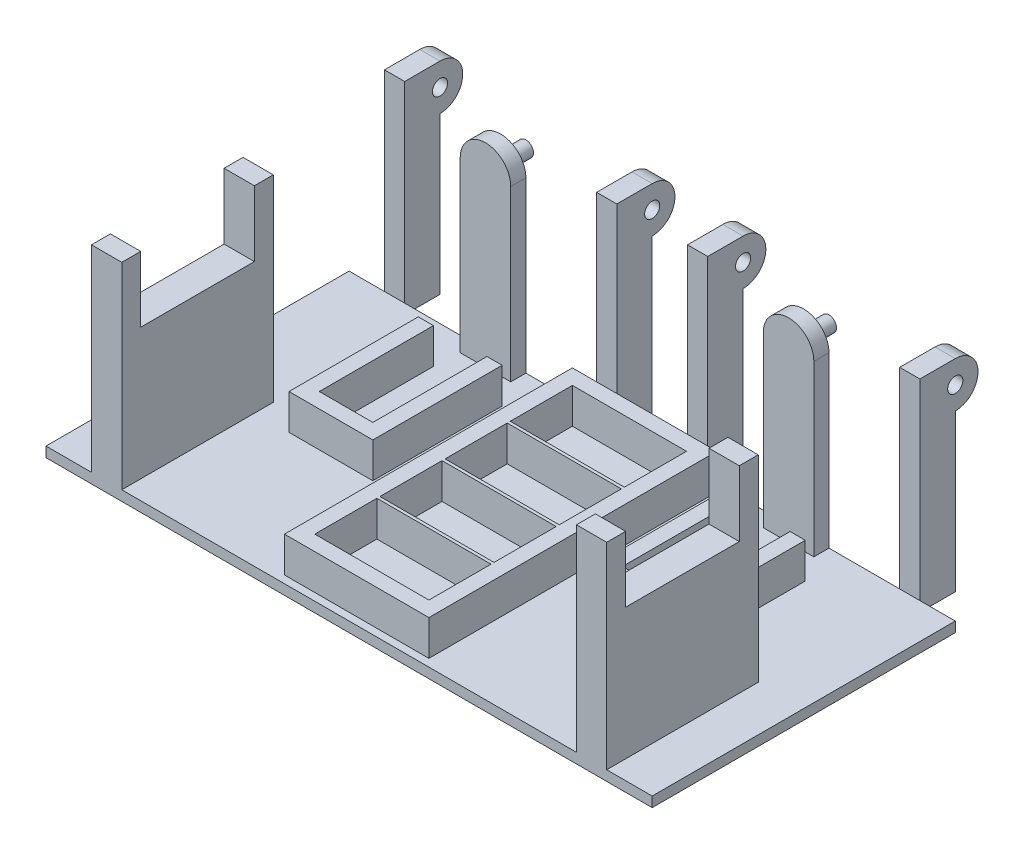
SolidWorks part; units mm, degrees
ref_plane "Front Plane" through (0, 0, 0) normal (0, 0, 1) x (1, 0, 0)
ref_plane "Top Plane" through (0, 0, 0) normal (0, 1, 0) x (1, 0, 0)
ref_plane "Right Plane" through (0, 0, 0) normal (1, 0, 0) x (0, 0, -1)
sketch "Sketch1" plane through (0, 0, 0) normal (0, 1, 0) x (1, 0, 0)
  line L0 (-60, -30) -> (-51, -30)
  line L1 (-60, -30) -> (60, -30)
  line L2 (-60, -30) -> (-60, 30)
  line L3 (-60, 30) -> (60, 30)
  line L4 (60, -30) -> (60, 30)
  line L5 (-60, -30) -> (60, 30) construction
  line L6 (-60, 30) -> (60, -30) construction
  line L7 (-51, -30) -> (-45, -30)
  line L8 (-45, -30) -> (-45, 0)
  line L9 (-45, 0) -> (-51, 0)
  line L10 (-51, 0) -> (-51, -30)
  line L11 (51, -30) -> (51, 0)
  line L12 (51, 0) -> (45, 0)
  line L13 (45, 0) -> (45, -30)
  line L14 (45, -30) -> (51, -30)
  line L15 (-38.3, 22) -> (-38.3, -3.6)
  line L16 (-38.3, -3.6) -> (-21.7, -3.6)
  line L17 (-21.7, -3.6) -> (-21.7, 22)
  line L18 (-21.7, 22) -> (-24.7, 22)
  line L19 (-24.7, 22) -> (-24.7, -0.6)
  line L20 (-24.7, -0.6) -> (-35.3, -0.6)
  line L21 (-35.3, -0.6) -> (-35.3, 22)
  line L22 (-35.3, 22) -> (-38.3, 22)
  line L23 (21.7, 22) -> (21.7, -3.6)
  line L24 (21.7, -3.6) -> (38.3, -3.6)
  line L25 (38.3, -3.6) -> (38.3, 22)
  line L26 (38.3, 22) -> (35.3, 22)
  line L27 (35.3, 22) -> (35.3, -0.6)
  line L28 (35.3, -0.6) -> (24.7, -0.6)
  line L29 (24.7, -0.6) -> (24.7, 22)
  line L30 (24.7, 22) -> (21.7, 22)
  line L31 (-25, 30) -> (-25, 27)
  line L32 (-25, 27) -> (-35, 27)
  line L33 (-35, 27) -> (-35, 30)
  line L34 (-35, 30) -> (-25, 30)
  line L35 (25, 30) -> (25, 27)
  line L36 (25, 27) -> (35, 27)
  line L37 (35, 27) -> (35, 30)
  line L38 (35, 30) -> (25, 30)
  line L39 (-53, 30) -> (-53, 37)
  line L40 (-53, 37) -> (-49, 37)
  line L41 (-49, 37) -> (-49, 30)
  line L42 (-7, 30) -> (-7, 37)
  line L43 (-7, 37) -> (-11, 37)
  line L44 (-11, 37) -> (-11, 30)
  line L45 (-11, 30) -> (-7, 30)
  line L46 (-53, 30) -> (-49, 30)
  line L47 (7, 30) -> (7, 37)
  line L48 (7, 37) -> (11, 37)
  line L49 (11, 37) -> (11, 30)
  line L50 (7, 30) -> (11, 30)
  line L51 (49, 30) -> (49, 37)
  line L52 (49, 37) -> (53, 37)
  line L53 (53, 37) -> (53, 30)
  line L54 (53, 30) -> (49, 30)
  line L55 (0, 0) -> (0, 30) construction
  line L64 (0, 0) -> (-60, 0) construction
  line L65 (-30, 0) -> (-30, 30) construction
  line L66 (0, 0) -> (60, 0) construction
  line L67 (30, 0) -> (30, 30) construction
  line L68 (-11.3, 13.2) -> (11.3, 13.2)
  line L69 (-11.3, -25.5) -> (11.3, -25.5)
  line L70 (-11.3, -25.5) -> (-11.3, 25.5)
  line L71 (-11.3, 25.5) -> (11.3, 25.5)
  line L72 (11.3, -25.5) -> (11.3, 25.5)
  line L73 (-11.3, -25.5) -> (11.3, 25.5) construction
  line L74 (-11.3, 25.5) -> (11.3, -25.5) construction
  line L75 (-14.3, -28.5) -> (14.3, -28.5)
  line L76 (-14.3, -28.5) -> (-14.3, 28.5)
  line L77 (-14.3, 28.5) -> (14.3, 28.5)
  line L78 (14.3, -28.5) -> (14.3, 28.5)
  line L79 (-14.3, -28.5) -> (14.3, 28.5) construction
  line L80 (-14.3, 28.5) -> (14.3, -28.5) construction
  line L81 (11.3, 13.2) -> (11.3, 12.6)
  line L82 (11.3, 12.6) -> (-11.3, 12.6)
  line L83 (-11.3, 12.6) -> (-11.3, 13.2)
  line L84 (-11.3, 0.3) -> (11.3, 0.3)
  line L85 (11.3, 0.3) -> (11.3, -0.3)
  line L86 (11.3, -0.3) -> (-11.3, -0.3)
  line L87 (-11.3, -0.3) -> (-11.3, 0.3)
  line L88 (-11.3, -12.6) -> (11.3, -12.6)
  line L89 (11.3, -12.6) -> (11.3, -13.2)
  line L90 (11.3, -13.2) -> (-11.3, -13.2)
  line L91 (-11.3, -13.2) -> (-11.3, -12.6)
  point P0 (0, 0)
  point P80 (36.8, 22)
  dimension "D1" = 120
  dimension "D2" = 60
  dimension "D3" = 9
  dimension "D4" = 6
  dimension "D5" = 30
  dimension "D6" = 6
  dimension "D7" = 30
  dimension "D8" = 9
  dimension "D9" = 7
  dimension "D10" = 4
  dimension "D11" = 7
  dimension "D12" = 7
  dimension "D13" = 4
  dimension "D14" = 7
  dimension "D15" = 4
  dimension "D16" = 7
  dimension "D17" = 4
  dimension "D18" = 7
  dimension "D19" = 7
  dimension "D20" = 3
  dimension "D21" = 10
  dimension "D22" = 5
  dimension "D23" = 22.6
  dimension "D24" = 10.6
  dimension "D25" = 25.6
  dimension "D26" = 3
  dimension "D27" = 3
  dimension "D28" = 3
  dimension "D29" = 25.6
  dimension "D30" = 3
  dimension "D31" = 25.6
  dimension "D32" = 3
  dimension "D33" = 3
  dimension "D34" = 10.6
  dimension "D35" = 3
  dimension "D36" = 10
  dimension "D37" = 7
  dimension "D38" = 5
  dimension "D39" = 5.3
  dimension "D40" = 5.3
  dimension "D41" = 5
  dimension "D42" = 5
  dimension "D43" = 51
  dimension "D44" = 22.6
  dimension "D45" = 3
  dimension "D46" = 3
  dimension "D47" = 0.6
  dimension "D48" = 12.3
  dimension "D49" = 0.6
  dimension "D50" = 12.3
  dimension "D51" = 12.3
  dimension "D52" = 12.3
  dimension "D53" = 25.6
extrude "Boss-Extrude1" add sketch "Sketch1" along normal blind 9 contours L29 L30 L23 L24 L25 L26 L27 L28 | L22 L15 L16 L17 L18 L19 L20 L21 region at (23.2, 0, -21.6949)
extrude "Boss-Extrude2" add sketch "Sketch1<3>" along normal blind 28 separate body contours L7 L8 L9 L10 | L12 L13 L14 L11
sketch "Sketch1<3>" plane through (0, 0, 0) normal (0, 1, 0) x (1, 0, 0) same geometry as "Sketch1"
extrude "Boss-Extrude3" add sketch "Sketch1<4>" along normal blind 40 separate body contours L40 L41 L46 L39 | L43 L44 L45 L42 | L48 L49 L50 L47 | L52 L53 L54 L51
sketch "Sketch1<4>" plane through (0, 0, 0) normal (0, 1, 0) x (1, 0, 0) same geometry as "Sketch1"
extrude "Boss-Extrude4" add sketch "Sketch1<5>" along normal blind 35.5 separate body contours L36 L37 L3 L35 | L31 L32 L33 L34 region at (30, 0, -28.5)
sketch "Sketch1<5>" plane through (0, 0, 0) normal (0, 1, 0) x (1, 0, 0) same geometry as "Sketch1"
extrude "Boss-Extrude5" add sketch "Sketch1<6>" along normal blind 2 contours L2 L3 L4 L1
sketch "Sketch1<6>" plane through (0, 0, 0) normal (0, 1, 0) x (1, 0, 0) same geometry as "Sketch1"
extrude "Boss-Extrude6" add sketch "Sketch1<8>" along normal blind 9 contours L72 L71 L70 L69 | L76 L77 L78 L75
sketch "Sketch1<8>" plane through (0, 0, 0) normal (0, 1, 0) x (1, 0, 0) same geometry as "Sketch1"
extrude "Boss-Extrude7" add sketch "Sketch1<9>" along normal blind 9 contours L68 L81 L82 L83 | L84 L85 L86 L87 | L88 L89 L90 L91
sketch "Sketch1<9>" plane through (0, 0, 0) normal (0, 1, 0) x (1, 0, 0) same geometry as "Sketch1"
sketch "Sketch2" plane through (0, 28, 0) normal (0, 1, 0) x (1, 0, 0)
  line L0 (-51, 0) -> (-45, 0)
  line L1 (-45, 0) -> (-45, -3.75)
  line L2 (-45, -30) -> (-45, 0) construction
  line L3 (-45, -3.75) -> (-51, -3.75)
  line L4 (-51, 0) -> (-51, -30) construction
  line L5 (-51, -3.75) -> (-51, 0)
  line L6 (-45, -30) -> (-45, -26.25)
  line L7 (-45, -26.25) -> (-51, -26.25)
  line L8 (-51, -26.25) -> (-51, -30)
  line L9 (-51, -30) -> (-45, -30)
  line L10 (45, 0) -> (51, 0)
  line L11 (51, 0) -> (51, -3.75)
  line L12 (51, -30) -> (51, 0) construction
  line L13 (51, -3.75) -> (45, -3.75)
  line L14 (45, 0) -> (45, -30) construction
  line L15 (45, -3.75) -> (45, 0)
  line L16 (45, -26.25) -> (51, -26.25)
  line L17 (51, -26.25) -> (51, -30)
  line L18 (51, -30) -> (45, -30)
  line L19 (45, -30) -> (45, -26.25)
  dimension "D1" = 22.5
  dimension "D2" = 3.75
  dimension "D3" = 22.5
extrude "Boss-Extrude8" add sketch "Sketch2" along normal blind 13
sketch "Sketch3" plane through (0, 0, -27) normal (0, 0, 1) x (1, 0, 0)
  line L0 (25, 35.5) -> (35, 35.5) construction
  line L1 (25, 35.5) -> (25, 2) construction
  line L2 (-25, 35.5) -> (-35, 35.5) construction
  line L3 (-35, 35.5) -> (-35, 2) construction
  line L4 (-35, 35.5) -> (-25, 35.5)
  line L5 (25, 35.5) -> (35, 35.5)
  arc A0 (35, 35.5) -> (25, 35.5) centre (30, 35.5) ccw
  arc A1 (-25, 35.5) -> (-35, 35.5) centre (-30, 35.5) ccw
  circle A2 centre (-30, 35.5) radius 1.5
  circle A3 centre (30, 35.5) radius 1.5
  line M3 (35, 35.5) -> (25, 35.5)
  dimension "D1" = 3
  dimension "D2" = 3
extrude "Boss-Extrude9" add sketch "Sketch3" against normal up to surface (3 mm away) contours A3 A0 M3 | A2 L4 A1 region at (-30, 37.769, -27) region at (30, 37.769, -27) up to face at (-30, 9.875, -30)
extrude "Boss-Extrude11" add sketch "Sketch3<5>" against normal blind 8 contours A3 | A2
sketch "Sketch3<5>" plane through (0, 0, -27) normal (0, 0, 1) x (1, 0, 0) same geometry as "Sketch3"
sketch "Sketch4" plane through (-53, 0, 0) normal (-1, 0, 0) x (0, 0, 1)
  line L2 (-30, 40) -> (-37, 40) construction
  circle A1 centre (-37, 35.5) radius 1.5
  circle A2 centre (-37, 35.5) radius 4.5
  dimension "D1" = 9
  dimension "D2" = 4.5
  dimension "D3" = 3
extrude "Boss-Extrude13" add sketch "Sketch4" against normal up to surface (4 mm away) contours A2 | A1 up to face at (-49, 16.4, -32.8)
extrude "Cut-Extrude2" cut sketch "Sketch4<4>" against normal up to surface (4 mm away) contours A1 up to face at (-49, 18.8333, -34.25)
sketch "Sketch4<4>" plane through (-53, 0, 0) normal (-1, 0, 0) x (0, 0, 1) same geometry as "Sketch4"
sketch "Sketch5" plane through (-11, 0, 0) normal (-1, 0, 0) x (0, 0, 1)
  circle A0 centre (-37, 35.5) radius 4.5
  circle A1 centre (-37, 35.5) radius 1.5
  dimension "D1" = 3
extrude "Boss-Extrude14" add sketch "Sketch5" against normal up to surface (4 mm away) up to face at (-7, 16.4, -32.8)
extrude "Cut-Extrude3" cut sketch "Sketch5<2>" against normal up to surface (4 mm away) contours A1 up to face at (-7, 18.8333, -34.25)
sketch "Sketch5<2>" plane through (-11, 0, 0) normal (-1, 0, 0) x (0, 0, 1) same geometry as "Sketch5"
sketch "Sketch7" plane through (7, 0, 0) normal (-1, 0, 0) x (0, 0, 1)
  circle A0 centre (-37, 35.5) radius 1.5
  circle A1 centre (-37, 35.5) radius 4.5
  dimension "D1" = 3
extrude "Boss-Extrude15" add sketch "Sketch7" against normal up to surface (4 mm away) up to face at (11, 16.4, -32.8)
extrude "Cut-Extrude4" cut sketch "Sketch7<2>" against normal up to surface (4 mm away) contours A0 up to face at (11, 18.8333, -34.25)
sketch "Sketch7<2>" plane through (7, 0, 0) normal (-1, 0, 0) x (0, 0, 1) same geometry as "Sketch7"
sketch "Sketch8" plane through (49, 0, 0) normal (-1, 0, 0) x (0, 0, 1)
  circle A0 centre (-37, 35.5) radius 1.5
  circle A1 centre (-37, 35.5) radius 4.5
  dimension "D1" = 3
extrude "Boss-Extrude16" add sketch "Sketch8" against normal up to surface (4 mm away) contours A0 | A1 up to face at (53, 16.4, -32.8)
extrude "Cut-Extrude5" cut sketch "Sketch8<4>" against normal up to surface (4 mm away) contours A0 up to face at (53, 18.8333, -34.25)
sketch "Sketch8<4>" plane through (49, 0, 0) normal (-1, 0, 0) x (0, 0, 1) same geometry as "Sketch8"
